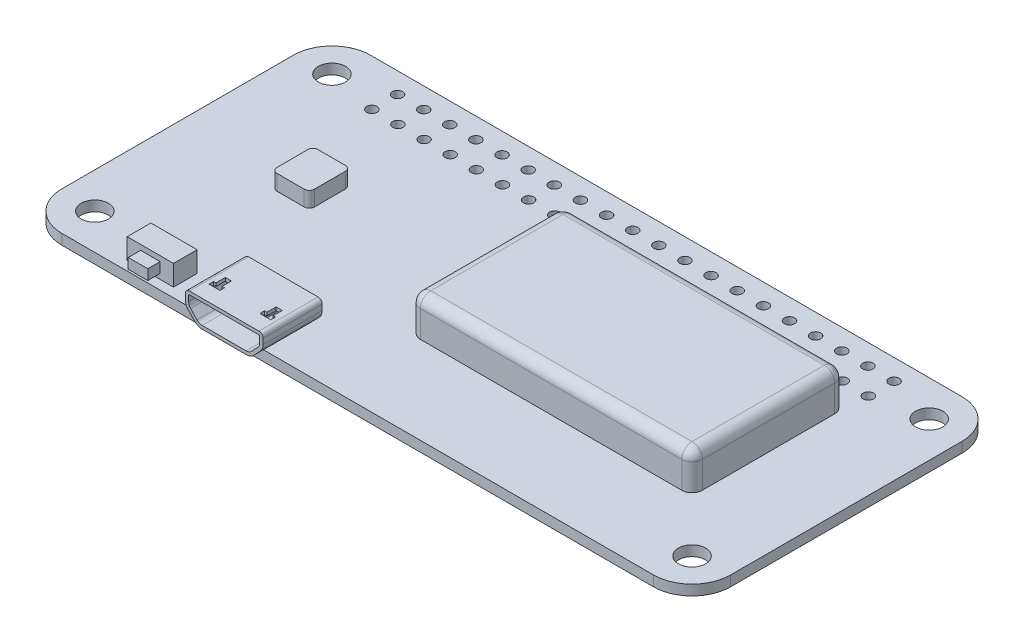
SolidWorks part; units mm, degrees
ref_plane "Front Plane" through (0, 0, 0) normal (0, 0, 1) x (1, 0, 0)
ref_plane "Top Plane" through (0, 0, 0) normal (0, 1, 0) x (1, 0, 0)
ref_plane "Right Plane" through (0, 0, 0) normal (1, 0, 0) x (0, 0, -1)
sketch "Sketch1" plane through (0, 0, 0) normal (0, 1, 0) x (1, 0, 0)
  line L1 (-28.75, 15) -> (28.75, 15)
  line L2 (-32.5, 11.25) -> (-32.5, -11.25)
  line L3 (-28.75, -15) -> (28.75, -15)
  line L4 (32.5, 11.25) -> (32.5, -11.25)
  line L5 (-32.5, 15) -> (32.5, -15) construction
  line L6 (-32.5, -15) -> (32.5, 15) construction
  arc A0 (-32.5, -11.25) -> (-28.75, -15) centre (-28.75, -11.25) ccw
  arc A1 (28.75, -15) -> (32.5, -11.25) centre (28.75, -11.25) ccw
  arc A2 (28.75, 15) -> (32.5, 11.25) centre (28.75, 11.25) cw
  arc A3 (-28.75, 15) -> (-32.5, 11.25) centre (-28.75, 11.25) ccw
  point P0 (0, 0)
  dimension "D3" = 3.75
  dimension "D1" = 65
  dimension "D2" = 30
extrude "Boss-Extrude1" add sketch "Sketch1" along normal blind 1 contours L1 A2 L4 A1 L3 A0 L2 A3
sketch "Sketch2" plane through (0, 1, 0) normal (0, 1, 0) x (1, 0, 0)
  line L0 (0, 15) -> (0, -15) construction
  line L1 (-28.75, 15) -> (28.75, 15) construction
  line L2 (-28.75, -15) -> (28.75, -15) construction
  line L3 (-32.5, 0) -> (32.5, 0) construction
  line L4 (-32.5, 11.25) -> (-32.5, -11.25) construction
  line L5 (32.5, 11.25) -> (32.5, -11.25) construction
  circle A0 centre (-29.025, 11.525) radius 1.325
  circle A2 centre (29.025, 11.525) radius 1.325
  circle A3 centre (29.025, -11.525) radius 1.325
  circle A4 centre (-29.025, -11.525) radius 1.325
  dimension "D1" = 2.65
  dimension "D2" = 2.15
  dimension "D3" = 2.15
extrude "Cut-Extrude1" cut sketch "Sketch2" against normal through all
sketch "Sketch3" plane through (0, 1, 0) normal (0, 1, 0) x (1, 0, 0)
  line L0 (-24.128, 13) -> (-24.128, 10.5) construction
  line L3 (-28.75, 15) -> (28.75, 15) construction
  line L5 (-32.5, 11.25) -> (-32.5, -11.25) construction
  circle A0 centre (-24.128, 13) radius 0.5
  circle A1 centre (-24.128, 10.5) radius 0.5
  dimension "D1" = 1
  dimension "D3" = 1.5
  dimension "D4" = 7.872
  dimension "D2" = 2.5
extrude "Cut-Extrude2" cut sketch "Sketch3" against normal through all
pattern_linear "LPattern1" count 20 spacing 2.54 along (1, 0, 0) of "Cut-Extrude2"
sketch "Sketch6" plane through (0, 1, 0) normal (0, 1, 0) x (1, 0, 0)
  line L0 (-28.75, -15) -> (28.75, -15) construction
  line L1 (-3.4, 8.35) -> (24, 8.35)
  line L2 (-3.4, 8.35) -> (-3.4, -6.5)
  line L3 (-3.4, -6.5) -> (24, -6.5)
  line L4 (24, 8.35) -> (24, -6.5)
  line L5 (-3.4, 8.35) -> (24, -6.5) construction
  line L6 (-3.4, -6.5) -> (24, 8.35) construction
  line L8 (32.5, 11.25) -> (32.5, -11.25) construction
  point P0 (10.3, 0.925)
  dimension "D1" = 27.4
  dimension "D2" = 8.5
  dimension "D3" = 8.5
  dimension "D4" = 14.85
sketch "Sketch15" plane through (0, 0, 15) normal (0, 0, 1) x (1, 0, 0)
  line L0 (-11.725, 1) -> (-11.725, 3.6) construction
  line L1 (-28.75, 1) -> (28.75, 1) construction
  line L2 (-15.1, 3.6) -> (-8.35, 3.6)
  line L3 (-7.95, 3.2) -> (-7.95, 2.6523)
  line L4 (-8.2286, 1.9598) -> (-8.8548, 1.3075)
  line L5 (-9.5762, 1) -> (-13.8738, 1)
  line L7 (-15.2214, 1.9598) -> (-14.5952, 1.3075)
  line L8 (-15.5, 3.2) -> (-15.5, 2.6523)
  line L9 (-32.5, 1) -> (-32.5, 0) construction
  arc A0 (-8.8548, 1.3075) -> (-9.5762, 1) centre (-9.5762, 2) cw
  arc A1 (-14.5952, 1.3075) -> (-13.8738, 1) centre (-13.8738, 2) ccw
  arc A2 (-7.95, 2.6523) -> (-8.2286, 1.9598) centre (-8.95, 2.6523) cw
  arc A3 (-15.2214, 1.9598) -> (-15.5, 2.6523) centre (-14.5, 2.6523) cw
  arc A4 (-8.35, 3.6) -> (-7.95, 3.2) centre (-8.35, 3.2) cw
  arc A5 (-15.5, 3.2) -> (-15.1, 3.6) centre (-15.1, 3.2) cw
  point P14 (-9.15, 1)
  point P17 (-14.3, 1)
  point P20 (-7.95, 2.25)
  point P23 (-15.5, 2.25)
  point P26 (-7.95, 3.6)
  point P29 (-15.5, 3.6)
  point P30 (-15.5, 2.9262)
  dimension "D6" = 1
  dimension "D7" = 0.4
  dimension "D1" = 7.55
  dimension "D2" = 2.6
  dimension "D3" = 1.35
  dimension "D4" = 5.15
  dimension "D5" = 17
extrude "Boss-Extrude6" add sketch "Sketch15" along normal blind 1.25 and the other way blind 4.5
sketch "Sketch16" plane through (0, 0, 16.25) normal (0, 0, 1) x (1, 0, 0)
  line L30 (-9.0857, 1.5291) -> (-8.4595, 2.1814)
  line L31 (-8.27, 2.6523) -> (-8.27, 3.2)
  line L32 (-8.35, 3.28) -> (-15.1, 3.28)
  line L33 (-15.18, 3.2) -> (-15.18, 2.6523)
  line L34 (-14.9905, 2.1814) -> (-14.3643, 1.5291)
  line L35 (-13.8738, 1.32) -> (-9.5762, 1.32)
  line L36 (-9.0857, 1.5291) -> (-8.4595, 2.1814)
  line L37 (-8.27, 2.6523) -> (-8.27, 3.2)
  line L38 (-8.35, 3.28) -> (-15.1, 3.28)
  line L39 (-15.18, 3.2) -> (-15.18, 2.6523)
  line L40 (-14.9905, 2.1814) -> (-14.3643, 1.5291)
  line L41 (-13.8738, 1.32) -> (-9.5762, 1.32)
  arc A30 (-9.5762, 1.32) -> (-9.0857, 1.5291) centre (-9.5762, 2) ccw
  arc A31 (-8.4595, 2.1814) -> (-8.27, 2.6523) centre (-8.95, 2.6523) ccw
  arc A32 (-8.27, 3.2) -> (-8.35, 3.28) centre (-8.35, 3.2) ccw
  arc A33 (-15.1, 3.28) -> (-15.18, 3.2) centre (-15.1, 3.2) ccw
  arc A34 (-15.18, 2.6523) -> (-14.9905, 2.1814) centre (-14.5, 2.6523) ccw
  arc A35 (-14.3643, 1.5291) -> (-13.8738, 1.32) centre (-13.8738, 2) ccw
  arc A36 (-9.5762, 1.32) -> (-9.0857, 1.5291) centre (-9.5762, 2) ccw
  arc A37 (-8.4595, 2.1814) -> (-8.27, 2.6523) centre (-8.95, 2.6523) ccw
  arc A38 (-8.27, 3.2) -> (-8.35, 3.28) centre (-8.35, 3.2) ccw
  arc A39 (-15.1, 3.28) -> (-15.18, 3.2) centre (-15.1, 3.2) ccw
  arc A40 (-15.18, 2.6523) -> (-14.9905, 2.1814) centre (-14.5, 2.6523) ccw
  arc A41 (-14.3643, 1.5291) -> (-13.8738, 1.32) centre (-13.8738, 2) ccw
  dimension "D2" = 0.32
extrude "Cut-Extrude9" cut sketch "Sketch16" against normal blind 5.25
sketch "Sketch17" plane through (0, 0, 11) normal (0, 0, 1) x (1, 0, 0)
  line L15 (-11.725, 1.32) -> (-11.725, 3.28) construction
  line L16 (-13.8738, 1.32) -> (-9.5762, 1.32) construction
  line L17 (-8.35, 3.28) -> (-15.1, 3.28) construction
  line L19 (-13.3, 2.52) -> (-10.15, 2.52)
  line L20 (-13.3, 2.52) -> (-13.3, 2.92)
  line L21 (-13.3, 2.92) -> (-10.15, 2.92)
  line L22 (-10.15, 2.52) -> (-10.15, 2.92)
  line L23 (-13.3, 2.52) -> (-10.15, 2.92) construction
  line L24 (-13.3, 2.92) -> (-10.15, 2.52) construction
  point P29 (-11.725, 2.72)
  dimension "D4" = 1.4
  dimension "D5" = 0.4
  dimension "D6" = 3.15
extrude "Boss-Extrude7" add sketch "Sketch17" along normal blind 3.5
sketch "Sketch18" plane through (0, 3.6, 0) normal (0, 1, 0) x (1, 0, 0)
  line L0 (-14.5, -13.37) -> (-14.5, -14.27)
  line L1 (-9.25, -13.37) -> (-9.25, -14.72) construction
  line L2 (-9.55, -13.37) -> (-9.55, -14.27)
  line L3 (-9.55, -14.27) -> (-9.775, -14.27)
  line L4 (-9.775, -14.27) -> (-9.775, -14.72)
  line L5 (-8.725, -14.27) -> (-8.725, -14.72)
  line L6 (-8.95, -14.27) -> (-8.725, -14.27)
  line L7 (-8.725, -14.72) -> (-9.775, -14.72)
  line L8 (-9.55, -13.37) -> (-8.95, -13.37)
  line L9 (-8.95, -13.37) -> (-8.95, -14.27)
  line L23 (-14.2, -13.37) -> (-14.2, -14.72) construction
  line L25 (-11.725, -16.25) -> (-11.725, -10.5) construction
  line L26 (-13.9, -13.37) -> (-14.5, -13.37)
  line L30 (-14.725, -14.72) -> (-13.675, -14.72)
  line L34 (-14.5, -14.27) -> (-14.725, -14.27)
  line L35 (-14.725, -14.27) -> (-14.725, -14.72)
  line L36 (-13.675, -14.27) -> (-13.675, -14.72)
  line L37 (-13.9, -14.27) -> (-13.675, -14.27)
  line L38 (-13.9, -13.37) -> (-13.9, -14.27)
  line L43 (-8.35, -16.25) -> (-15.1, -16.25) construction
  line L44 (-8.35, -10.5) -> (-15.1, -10.5) construction
  point P77 (-11.725, -16.25)
  point P80 (-11.725, -10.5)
  point P83 (-14.2, -14.72)
  point P85 (-14.2, -13.37)
  dimension "D7" = 1.53
  dimension "D8" = 1.05
  dimension "D9" = 0.6
  dimension "D10" = 1.35
  dimension "D11" = 0.9
  dimension "D13" = 2.475
extrude "Cut-Extrude10" cut sketch "Sketch18" against normal up to next
sketch "Sketch22" plane through (0, 1, 0) normal (0, 1, 0) x (1, 0, 0)
  line L1 (-22.35, 3) -> (-18.7, 3)
  line L2 (-22.35, 3) -> (-22.35, -1)
  line L3 (-22.35, -1) -> (-18.7, -1)
  line L4 (-18.7, 3) -> (-18.7, -1)
  line L5 (-28.75, 15) -> (28.75, 15) construction
  line L6 (-32.5, 11.25) -> (-32.5, -11.25) construction
  point P4 (-18.7, 1)
  dimension "D1" = 3.65
  dimension "D2" = 4
  dimension "D3" = 13.8
  dimension "D4" = 12
extrude "Boss-Extrude11" add sketch "Sketch22" along normal blind 1.5
fillet "Fillet5" radius 0.5 4 edges at (-18.7, 1.75, -3) (-22.35, 1.75, -3) (-18.7, 1.75, 1) (-22.35, 1.75, 1)
extrude "Boss-Extrude12" add sketch "Sketch6" along normal blind 3.6
fillet "Fillet4" radius 1 8 edges at (-3.4, 4.6, -0.925) (10.3, 4.6, 6.5) (24, 4.6, -0.925) (10.3, 4.6, -8.35) (-3.4, 2.8, -8.35) (24, 2.8, -8.35) (-3.4, 2.8, 6.5) (24, 2.8, 6.5)
sketch "Sketch23" plane through (0, 1, 0) normal (0, 1, 0) x (1, 0, 0)
  line L0 (-15.5, -10.5) -> (-15.5, -16.25) construction
  line L1 (-23.3, -11.8) -> (-18.8, -11.8)
  line L2 (-23.3, -11.8) -> (-23.3, -14.1)
  line L3 (-23.3, -14.1) -> (-18.8, -14.1)
  line L4 (-18.8, -11.8) -> (-18.8, -14.1)
  line L7 (-28.75, -15) -> (-13.8738, -15) construction
  dimension "D1" = 4.5
  dimension "D2" = 2.3
  dimension "D3" = 3.3
  dimension "D4" = 3.2
extrude "Boss-Extrude13" add sketch "Sketch23" along normal blind 2
sketch "Sketch24" plane through (0, 0, 14.1) normal (0, 0, 1) x (1, 0, 0)
  line L0 (-21.05, 3) -> (-21.05, 1) construction
  line L1 (-23.3, 3) -> (-18.8, 3) construction
  line L2 (-23.3, 1) -> (-18.8, 1) construction
  line L4 (-22, 2.5) -> (-20.1, 2.5)
  line L5 (-22, 2.5) -> (-22, 1.5)
  line L6 (-22, 1.5) -> (-20.1, 1.5)
  line L7 (-20.1, 2.5) -> (-20.1, 1.5)
  line L8 (-22, 2.5) -> (-20.1, 1.5) construction
  line L9 (-22, 1.5) -> (-20.1, 2.5) construction
  point P6 (-21.05, 2)
  point P11 (-22, 2)
  dimension "D1" = 1.9
  dimension "D2" = 1
extrude "Boss-Extrude14" add sketch "Sketch24" along normal blind 1.2
sketch "Sketch25" plane through (0, 0, 0) normal (0, -1, 0) x (1, 0, 0)
  line L0 (-28.75, 15) -> (28.75, 15) construction
  line L1 (-22.4, 12.1) -> (-19.1, 12.1)
  line L2 (-22.4, 12.1) -> (-22.4, 11.17)
  line L3 (-22.4, 11.17) -> (-19.1, 11.17)
  line L4 (-19.1, 12.1) -> (-19.1, 11.17)
  line L5 (-22.4, 9.6) -> (-19.1, 9.6)
  line L6 (-22.4, 9.6) -> (-22.4, 8.67)
  line L7 (-22.4, 8.67) -> (-19.1, 8.67)
  line L8 (-19.1, 9.6) -> (-19.1, 8.67)
  line L9 (-32.5, -11.25) -> (-32.5, 11.25) construction
  point P10 (-22.4, 9.135)
  dimension "D1" = 2.9
  dimension "D2" = 3.43
  dimension "D3" = 3.3
  dimension "D4" = 10.1
  dimension "D5" = 0.93
extrude "Boss-Extrude15" add sketch "Sketch25" along normal blind 1
fillet "Fillet6" radius 0.5 2 edges at (-19.1, -1, 9.135) (-19.1, -1, 11.635)
sketch "Sketch26" plane through (0, -1, 0) normal (0, -1, 0) x (1, 0, 0)
  line L0 (-22.4, 11.17) -> (-19.6, 11.17) construction
  line L1 (-22.1, 11.17) -> (-21.2, 11.17)
  line L2 (-22.1, 11.17) -> (-22.1, 12.1)
  line L3 (-22.1, 12.1) -> (-21.2, 12.1)
  line L4 (-21.2, 11.17) -> (-21.2, 12.1)
  line L5 (-19.6, 12.1) -> (-22.4, 12.1) construction
  line L6 (-22.4, 8.67) -> (-19.6, 8.67) construction
  line L7 (-22.1, 8.67) -> (-21.2, 8.67)
  line L8 (-22.1, 8.67) -> (-22.1, 9.6)
  line L9 (-22.1, 9.6) -> (-21.2, 9.6)
  line L10 (-21.2, 8.67) -> (-21.2, 9.6)
  line L11 (-19.6, 9.6) -> (-22.4, 9.6) construction
  line L12 (-22.4, 12.1) -> (-22.4, 11.17) construction
  dimension "D1" = 0.9
  dimension "D2" = 0.3
extrude "Boss-Extrude16" add sketch "Sketch26" along normal blind 0.7
fillet "Fillet7" radius 0.5 4 edges at (-22.1, -1.7, 11.635) (-21.2, -1.7, 11.635) (-22.1, -1.7, 9.135) (-21.2, -1.7, 9.135)
sketch "Sketch27" plane through (0, 0, 0) normal (0, -1, 0) x (1, 0, 0)
  line L0 (-29.5, 6.75) -> (-29.5, -6.75) construction
  line L1 (-30.5, 7.4) -> (-28.5, 7.4)
  line L2 (-30.5, 7.4) -> (-30.5, 6.1)
  line L3 (-30.5, 6.1) -> (-28.5, 6.1)
  line L4 (-28.5, 7.4) -> (-28.5, 6.1)
  line L5 (-30.5, 7.4) -> (-28.5, 6.1) construction
  line L6 (-30.5, 6.1) -> (-28.5, 7.4) construction
  line L7 (-30.5, 2.9) -> (-28.5, 2.9)
  line L8 (-30.5, 2.9) -> (-30.5, 1.6)
  line L9 (-30.5, 1.6) -> (-28.5, 1.6)
  line L10 (-28.5, 2.9) -> (-28.5, 1.6)
  line L11 (-30.5, 2.9) -> (-28.5, 1.6) construction
  line L12 (-30.5, 1.6) -> (-28.5, 2.9) construction
  line L13 (-30.5, -1.6) -> (-28.5, -1.6)
  line L14 (-30.5, -1.6) -> (-30.5, -2.9)
  line L15 (-30.5, -2.9) -> (-28.5, -2.9)
  line L16 (-28.5, -1.6) -> (-28.5, -2.9)
  line L17 (-30.5, -1.6) -> (-28.5, -2.9) construction
  line L18 (-30.5, -2.9) -> (-28.5, -1.6) construction
  line L19 (-30.5, -6.1) -> (-28.5, -6.1)
  line L20 (-30.5, -6.1) -> (-30.5, -7.4)
  line L21 (-30.5, -7.4) -> (-28.5, -7.4)
  line L22 (-28.5, -6.1) -> (-28.5, -7.4)
  line L23 (-30.5, -6.1) -> (-28.5, -7.4) construction
  line L24 (-30.5, -7.4) -> (-28.5, -6.1) construction
  line L25 (-29.5, 15) -> (-29.5, -15) construction
  line L26 (-28.75, 15) -> (28.75, 15) construction
  line L27 (-28.75, -15) -> (28.75, -15) construction
  line L28 (-32.5, -11.25) -> (-32.5, 11.25) construction
  point P0 (-29.5, 6.75)
  point P5 (-29.5, 2.25)
  point P10 (-29.5, -2.25)
  point P15 (-29.5, -6.75)
  point P22 (-29.5, 0)
  point P23 (-29.5, 0)
  dimension "D1" = 13.5
  dimension "D2" = 1.3
  dimension "D3" = 4.5
  dimension "D4" = 4.5
  dimension "D5" = 2
  dimension "D6" = 4
extrude "Boss-Extrude17" add sketch "Sketch27" along normal blind 0.2
sketch "Sketch28" plane through (0, -0.2, 0) normal (0, -1, 0) x (1, 0, 0)
  line L0 (-29.5, 7.4) -> (-29.5, -7.4) construction
  line L1 (-28.5, 7.4) -> (-30.5, 7.4) construction
  line L2 (-30.5, -7.4) -> (-28.5, -7.4) construction
  line L3 (-28.5, 2.9) -> (-30.5, 2.9) construction
  line L4 (-28.9, 6.1) -> (-30.1, 6.1)
  line L5 (-28.9, 6.1) -> (-28.9, 7.4)
  line L6 (-28.9, 7.4) -> (-30.1, 7.4)
  line L7 (-30.1, 6.1) -> (-30.1, 7.4)
  line L8 (-28.9, 6.1) -> (-30.1, 7.4) construction
  line L9 (-28.9, 7.4) -> (-30.1, 6.1) construction
  line L10 (-28.9, 1.6) -> (-30.1, 1.6)
  line L11 (-28.9, 1.6) -> (-28.9, 2.9)
  line L12 (-28.9, 2.9) -> (-30.1, 2.9)
  line L13 (-30.1, 1.6) -> (-30.1, 2.9)
  line L14 (-28.9, 1.6) -> (-30.1, 2.9) construction
  line L15 (-28.9, 2.9) -> (-30.1, 1.6) construction
  line L16 (-28.5, -1.6) -> (-30.5, -1.6) construction
  line L17 (-28.9, -2.9) -> (-30.1, -2.9)
  line L18 (-28.9, -2.9) -> (-28.9, -1.6)
  line L19 (-28.9, -1.6) -> (-30.1, -1.6)
  line L20 (-30.1, -2.9) -> (-30.1, -1.6)
  line L21 (-28.9, -2.9) -> (-30.1, -1.6) construction
  line L22 (-28.9, -1.6) -> (-30.1, -2.9) construction
  line L23 (-28.5, -6.1) -> (-30.5, -6.1) construction
  line L24 (-28.9, -7.4) -> (-30.1, -7.4)
  line L25 (-28.9, -7.4) -> (-28.9, -6.1)
  line L26 (-28.9, -6.1) -> (-30.1, -6.1)
  line L27 (-30.1, -7.4) -> (-30.1, -6.1)
  line L28 (-28.9, -7.4) -> (-30.1, -6.1) construction
  line L29 (-28.9, -6.1) -> (-30.1, -7.4) construction
  line L30 (-30.5, -2.9) -> (-28.5, -2.9) construction
  line L31 (-30.5, 1.6) -> (-28.5, 1.6) construction
  line L32 (-30.5, 6.1) -> (-28.5, 6.1) construction
  point P6 (-29.5, 6.75)
  point P11 (-29.5, 2.25)
  point P18 (-29.5, -2.25)
  point P25 (-29.5, -6.75)
  dimension "D1" = 1.2
extrude "Boss-Extrude18" add sketch "Sketch28" along normal blind 0.6
